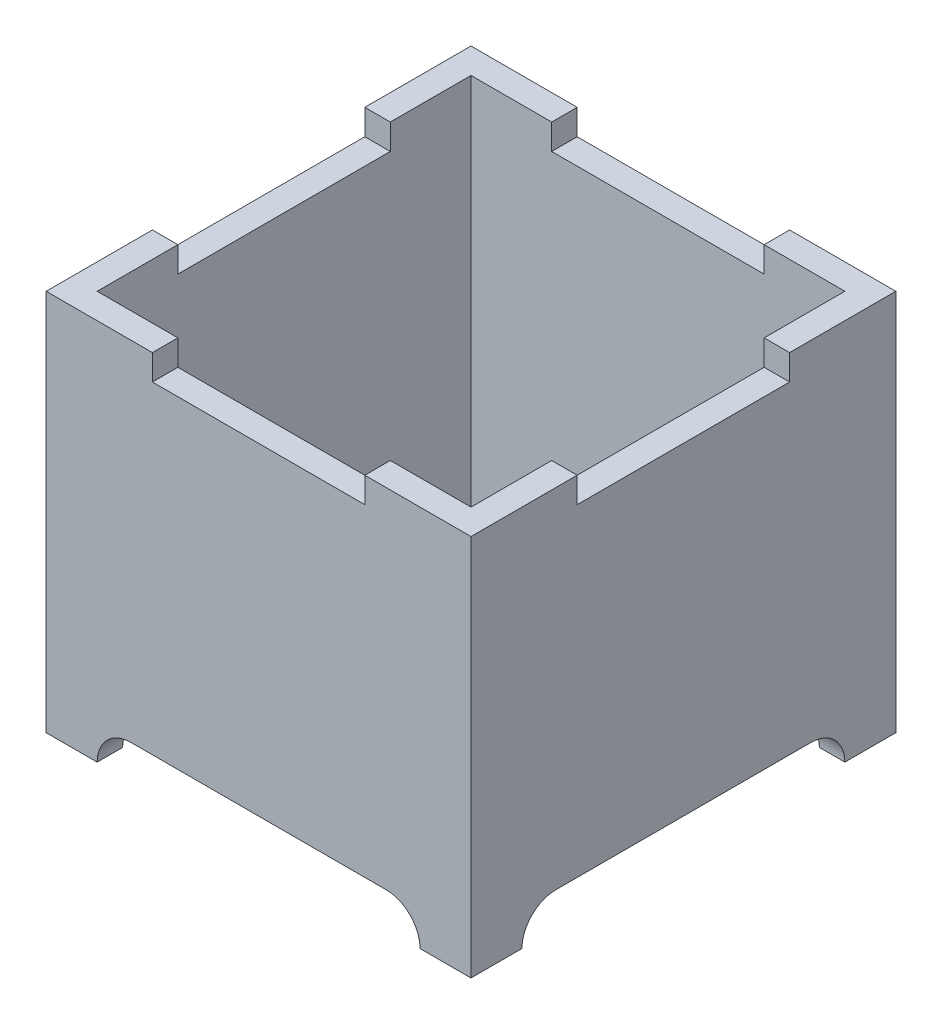
SolidWorks part; units mm, degrees
ref_plane "Plan de face" through (0, 0, 0) normal (0, 0, 1) x (1, 0, 0)
ref_plane "Plan de dessus" through (0, 0, 0) normal (0, 1, 0) x (1, 0, 0)
ref_plane "Plan de droite" through (0, 0, 0) normal (1, 0, 0) x (0, 0, -1)
sketch "Esquisse2" plane through (0, 0, 0) normal (0, 1, 0) x (1, 0, 0)
  line L1 (0, 0) -> (50, 0)
  line L2 (0, 0) -> (0, 50)
  line L3 (0, 50) -> (50, 50)
  line L4 (50, 0) -> (50, 50)
extrude "Boss.-Extru.2" add sketch "Esquisse2" against normal blind 45
sketch "Esquisse4" plane through (0, 0, 0) normal (0, 1, 0) x (1, 0, 0)
  line L0 (25, 50) -> (25, 0) construction
  line L1 (50, 50) -> (47, 50) construction
  line L2 (50, 50) -> (0, 50) construction
  line L11 (0, 0) -> (50, 0) construction
  line L12 (47, 50) -> (47, 47) construction
  line L14 (3, 3) -> (47, 3)
  line L15 (3, 3) -> (3, 47)
  line L16 (3, 47) -> (47, 47)
  line L17 (47, 3) -> (47, 47)
  line L18 (3, 3) -> (47, 47) construction
  line L19 (3, 47) -> (47, 3) construction
  point P8 (25, 25)
extrude "Enlèv. mat.-Extru.3" cut sketch "Esquisse4" against normal blind 45
sketch "Esquisse5" plane through (0, 0, 0) normal (0, 0, 1) x (1, 0, 0)
  line L0 (12.5, 0) -> (12.5, -3)
  line L1 (0, 0) -> (50, 0) construction
  line L2 (0, 0) -> (25, 0) construction
  line L3 (25, 0) -> (50, 0) construction
  line L4 (37.5, 0) -> (37.5, -3)
  line L5 (37.5, -3) -> (12.5, -3)
  line L6 (12.5, 0) -> (37.5, 0)
extrude "Enlèv. mat.-Extru.4" cut sketch "Esquisse5" against normal blind 57
sketch "Esquisse6" plane through (50, 0, 0) normal (1, 0, 0) x (0, 0, -1)
  line L0 (0, 0) -> (25, 0) construction
  line L1 (0, 0) -> (50, 0) construction
  line L2 (25, 0) -> (50, 0) construction
  line L3 (12.5, 0) -> (12.5, -3)
  line L4 (37.5, 0) -> (37.5, -3)
  line L5 (37.5, -3) -> (12.5, -3)
  line L6 (12.5, 0) -> (37.5, 0)
extrude "Enlèv. mat.-Extru.5" cut sketch "Esquisse6" against normal blind 57
sketch "Esquisse7" plane through (0, 0, 0) normal (0, 0, 1) x (1, 0, 0)
  line L0 (0, -45) -> (6, -45) construction
  line L1 (0, -45) -> (50, -45) construction
  line L2 (50, -45) -> (44, -45) construction
  line L3 (44, -45) -> (44, -41) construction
  line L5 (44, -41) -> (6, -41)
  line L6 (44, -41) -> (44, -45)
  line L7 (44, -45) -> (6, -45)
  line L8 (6, -41) -> (6, -45)
extrude "Enlèv. mat.-Extru.6" cut sketch "Esquisse7" against normal blind 57
sketch "Esquisse8" plane through (50, 0, 0) normal (1, 0, 0) x (0, 0, -1)
  line L0 (0, -45) -> (6, -45) construction
  line L1 (0, -45) -> (50, -45) construction
  line L2 (50, -45) -> (44, -45) construction
  line L3 (44, -45) -> (44, -41) construction
  line L5 (44, -41) -> (6, -41)
  line L6 (44, -41) -> (44, -45)
  line L7 (44, -45) -> (6, -45)
  line L8 (6, -41) -> (6, -45)
extrude "Enlèv. mat.-Extru.7" cut sketch "Esquisse8" against normal blind 57
fillet "Congé1" radius 4 8 edges at (44, -41, -48.5) (44, -41, -1.5) (6, -41, -1.5) (1.5, -41, -6) (1.5, -41, -44) (6, -41, -48.5) (48.5, -41, -44) (48.5, -41, -6)
